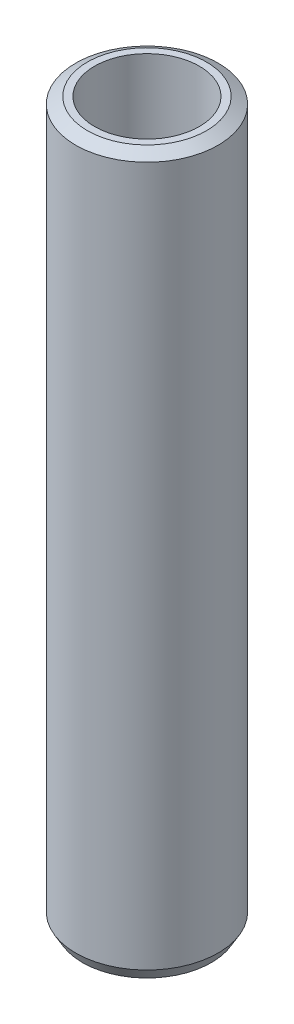
SolidWorks part; units mm, degrees
ref_plane "Front Plane" through (0, 0, 0) normal (0, 0, 1) x (1, 0, 0)
ref_plane "Top Plane" through (0, 0, 0) normal (0, 1, 0) x (1, 0, 0)
ref_plane "Right Plane" through (0, 0, 0) normal (1, 0, 0) x (0, 0, -1)
sketch "Sketch1" plane through (0, 0, 0) normal (0, 1, 0) x (1, 0, 0)
  circle A0 centre (0, 0) radius 52.5
  dimension "SHAFT_OD" = 105
extrude "Boss-Extrude1" add sketch "Sketch1" along normal blind 529.3599
sketch "Sketch2" plane through (0, 0, 0) normal (0, 1, 0) x (1, 0, 0)
  circle A0 centre (0, 0) radius 38.6206
  dimension "BORE_D" = 77.2411
extrude "Cut-Extrude1" cut sketch "Sketch2" along normal through all
chamfer "Chamfer1" distance 4.9656 angle 60 2 edges at (0, 529.3599, 52.5) (0, 0, 52.5) first distance on face at (0, 529.3599, 52.5) first distance on face at (0, 0, 38.6206)
